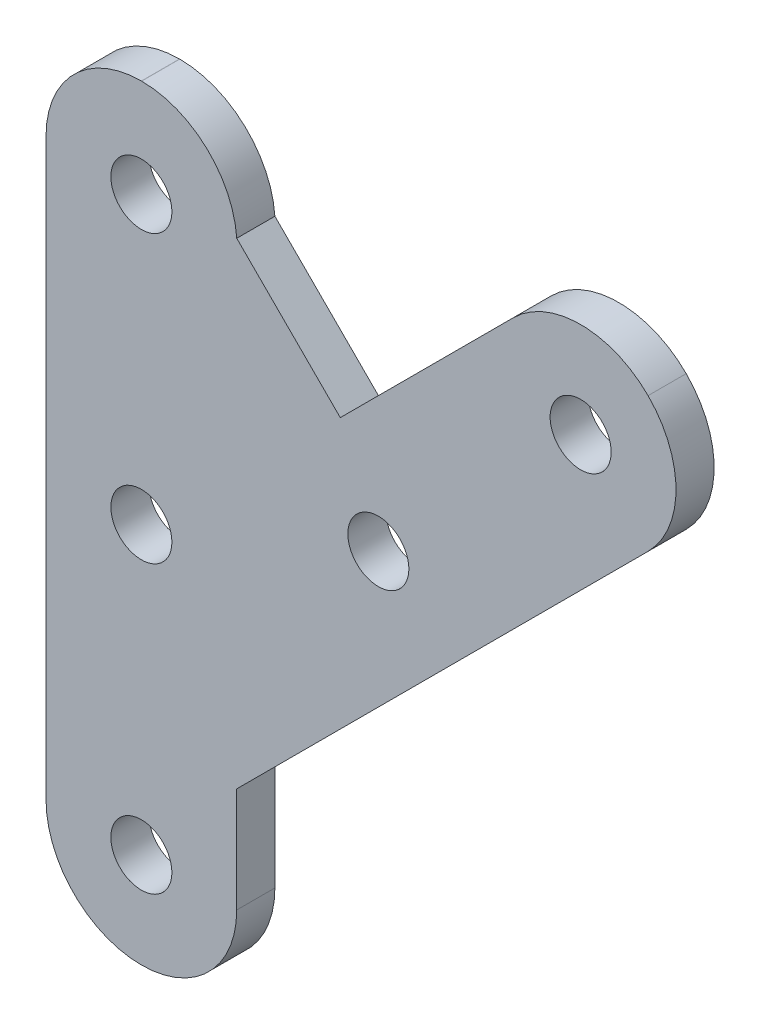
SolidWorks part; units mm, degrees
material "5052-O"
ref_plane "正面" through (0, 0, 0) normal (0, 0, 1) x (1, 0, 0)
ref_plane "平面" through (0, 0, 0) normal (0, 1, 0) x (1, 0, 0)
ref_plane "右側面" through (0, 0, 0) normal (1, 0, 0) x (0, 0, -1)
sketch "ｽｹｯﾁ1" plane through (0, 0, 0) normal (0, 0, 1) x (1, 0, 0)
  line L0 (-3.8279, 2.447) -> (-3.8279, -19.7772)
  line L5 (-3.8279, -19.7772) -> (6.1721, -19.7772)
  line L6 (6.1721, -19.7772) -> (6.1721, -9.2772)
  line L7 (6.1721, -9.2772) -> (31.2744, 15.8251)
  line L8 (31.2744, 15.8251) -> (24.2034, 22.8962)
  line L9 (24.2034, 22.8962) -> (-3.8279, -5.1351)
  line L10 (-3.8279, -5.1351) -> (-3.8279, 2.447)
  line L11 (-3.8279, -5.1351) -> (-3.8279, 20.3649)
  line L12 (6.1721, -9.2772) -> (6.1721, 20.3649)
  line L13 (6.1721, 20.3649) -> (-3.8279, 20.3649)
  line L14 (6.1721, 15.7228) -> (11.6011, 10.2939)
  dimension "D1" = 10.5
  dimension "D2" = 10
  dimension "D3" = 10
  dimension "D4" = 360
  dimension "D5" = 135
  dimension "D6" = 315
  dimension "D7" = 35.5
  dimension "D8" = 90
  dimension "D9" = 180
  dimension "D10" = 135
  dimension "D11" = 25.5
  dimension "D12" = 10
  dimension "D13" = 25
  dimension "D14" = 90
extrude "ﾎﾞｽ - 押し出し1" add sketch "ｽｹｯﾁ1" along normal mid plane 2
fillet "ﾌｨﾚｯﾄ1" radius 5 6 edges at (24.2034, 22.8962, 0) (-3.8279, -19.7772, 0) (6.1721, -19.7772, 0) (31.2744, 15.8251, 0) (-3.8279, 20.3649, 0) (6.1721, 20.3649, 0)
sketch "ｽｹｯﾁ2" plane through (0, 0, 1) normal (0, 0, 1) x (1, 0, 0)
  line L0 (6.1721, -9.2772) -> (-3.8279, -9.2772)
  line L2 (-3.8279, 15.3649) -> (-3.8279, -14.7772) construction
  line L3 (6.1721, 15.7228) -> (6.1721, -9.2772)
  line L4 (13.2432, -2.2061) -> (6.1721, 4.8649)
  line L6 (6.1721, -9.2772) -> (27.7389, 12.2896) construction
  circle A6 centre (1.1714, -14.7772) radius 1.6
  circle A8 centre (13.5968, 5.2185) radius 1.6
  circle A9 centre (24.2034, 15.8251) radius 1.6
  circle A10 centre (1.1714, 0.2228) radius 1.6
  circle A11 centre (1.1714, 15.2228) radius 1.6
  dimension "D2" = 3.2
  dimension "D3" = 5.5
  dimension "D4" = 3.2
  dimension "D5" = 25.5
  dimension "D7" = 5.5
  dimension "D6" = 5
  dimension "D1" = 2
  dimension "D8" = 3
extrude "ｶｯﾄ - 押し出し1" cut sketch "ｽｹｯﾁ2" against normal through all
